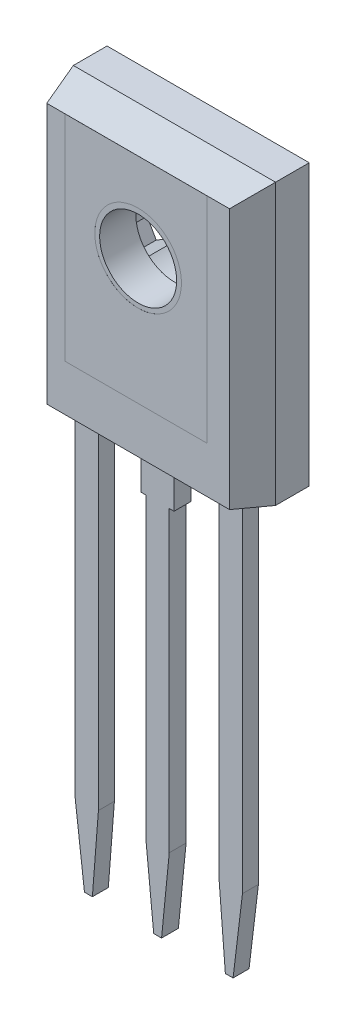
SolidWorks part; units mm, degrees
ref_plane "Front Plane" through (0, 0, 0) normal (0, 0, 1) x (1, 0, 0)
ref_plane "Top Plane" through (0, 0, 0) normal (0, 1, 0) x (1, 0, 0)
ref_plane "Right Plane" through (0, 0, 0) normal (1, 0, 0) x (0, 0, -1)
sketch "Sketch1" plane through (0, 0, 0) normal (0, 0, 1) x (1, 0, 0)
  line L1 (-3.9, 5.4) -> (3.9, 5.4)
  line L2 (-3.9, 5.4) -> (-3.9, -5.4)
  line L3 (-3.9, -5.4) -> (3.9, -5.4)
  line L4 (3.9, 5.4) -> (3.9, -5.4)
  line L5 (-3.9, 5.4) -> (3.9, -5.4) construction
  line L6 (-3.9, -5.4) -> (3.9, 5.4) construction
  circle A0 centre (0, 1.6) radius 1.6
  point P0 (0, 0)
extrude "Boss-Extrude2" add sketch "Sketch1" along normal blind 1.3
sketch "Sketch3" plane through (0, 0, 1.3) normal (0, 0, 1) x (1, 0, 0)
  line L1 (-3.9, -5.4) -> (3.9, -5.4)
  line L2 (-3.9, -5.4) -> (-3.9, 5.4)
  line L3 (-3.9, 5.4) -> (3.9, 5.4)
  line L4 (3.9, -5.4) -> (3.9, 5.4)
extrude "Boss-Extrude3" add sketch "Sketch3" along normal blind 1.4 separate body
sketch "Sketch2" plane through (0, 0, 1.3) normal (0, 0, 1) x (1, 0, 0)
  line L0 (0, 0) -> (0, 4.4749) construction
  line L1 (2.5017, 0.733) -> (1.5662, 1.2731)
  line L2 (0, 4.2) -> (0.5, 4.2)
  line L3 (0, 4.2) -> (-0.5, 4.2)
  line L4 (-0.5, 4.2) -> (-0.5, 3.1199)
  line L5 (0.5, 4.2) -> (0.5, 3.1199)
  line L6 (-0.5, 3.1199) -> (0.5, 3.1199)
  line L7 (2.2517, 0.3) -> (2.5017, 0.733)
  line L8 (2.2517, 0.3) -> (2.0017, -0.133)
  line L9 (2.0017, -0.133) -> (1.0662, 0.4071)
  line L10 (1.5662, 1.2731) -> (1.0662, 0.4071)
  line L11 (-2.0017, -0.133) -> (-1.0662, 0.4071)
  line L12 (-2.2517, 0.3) -> (-2.0017, -0.133)
  line L13 (-2.2517, 0.3) -> (-2.5017, 0.733)
  line L14 (-2.5017, 0.733) -> (-1.5662, 1.2731)
  line L15 (-1.0662, 0.4071) -> (-1.5662, 1.2731)
  circle A0 centre (0, 1.6) radius 1.6 construction
  dimension "D1" = 3
extrude "Cut-Extrude2" cut sketch "Sketch2" against normal blind 2.5
chamfer "Chamfer2" distance 1.4 angle 15 4 edges at (0, 5.4, 2.7) (3.9, 0, 2.7) (0, -5.4, 2.7) (-3.9, 0, 2.7) first distance on face at (0, 5.4, 2) first distance on face at (3.9, 0, 2) first distance on face at (0, -5.4, 2) first distance on face at (-3.9, 0, 2)
sketch "Sketch9" plane through (0, 0, 2.7) normal (0, 0, 1) x (1, 0, 0)
  line L0 (3.5249, 5.0249) -> (-3.5249, 5.0249) construction
  line L1 (-2.815, 5.0249) -> (2.657, 5.0249)
  line L2 (-2.815, 5.0249) -> (-2.815, -3.2408)
  line L3 (-2.815, -3.2408) -> (2.657, -3.2408)
  line L4 (2.657, 5.0249) -> (2.657, -3.2408)
extrude "Boss-Extrude7" add sketch "Sketch9" along normal blind 0.001 separate body
sketch "Sketch4" plane through (0, 0, 1.3) normal (0, 0, -1) x (-1, 0, 0)
  circle A0 centre (0, 1.6) radius 1.4862
extrude "Cut-Extrude3" cut sketch "Sketch4" against normal blind 4.4
sketch "Sketch5" plane through (0, -5.4, 0) normal (0, -1, 0) x (1, 0, 0)
  line L0 (3.9, 0) -> (-3.9, 1.3) construction
  line L1 (-3.9, 0) -> (3.9, 1.3) construction
  line L2 (3.9, 1.3) -> (3.9, 0) construction
  line L3 (3.9, 0) -> (-3.9, 1.3) construction
  line L4 (0.635, 1.3) -> (-0.635, 1.3)
  line L5 (0.635, 1.3) -> (0.635, 1.95)
  line L6 (0.635, 1.95) -> (-0.635, 1.95)
  line L7 (-0.635, 1.3) -> (-0.635, 1.95)
  line L8 (0.635, 1.3) -> (-0.635, 1.95) construction
  line L9 (0.635, 1.95) -> (-0.635, 1.3) construction
  line L10 (-3.9, 1.3) -> (-3.9, 0) construction
  line L11 (-3.9, 0) -> (0, 0) construction
  line L12 (-3.9, 0) -> (3.9, 0) construction
  line L13 (0, 0) -> (0, 1.3) construction
  line L14 (-3.9, 1.3) -> (3.9, 1.3) construction
  point P6 (0, 1.625)
extrude "Boss-Extrude4" add sketch "Sketch5" along normal blind 1.5 and the other way blind 1.5 separate body
sketch "Sketch7" plane through (0, -5.4, 0) normal (0, -1, 0) x (1, 0, 0)
  line L1 (-3.228, 1.2882) -> (-2.328, 1.2882)
  line L2 (-3.228, 1.2882) -> (-3.228, 1.9044)
  line L3 (-3.228, 1.9044) -> (-2.328, 1.9044)
  line L4 (-2.328, 1.2882) -> (-2.328, 1.9044)
  line L5 (-3.228, 1.2882) -> (-2.328, 1.9044) construction
  line L6 (-3.228, 1.9044) -> (-2.328, 1.2882) construction
  point P0 (-2.778, 1.5963)
extrude "Boss-Extrude5" add sketch "Sketch7" along normal blind 16 and the other way blind 1.5
mirror "Mirror1" about plane through (0, 0, 0) normal (1, 0, 0) of "Boss-Extrude5"
sketch "Sketch8" plane through (0, -6.9, 0) normal (0, -1, 0) x (1, 0, 0)
  point P6 (-0.0842, 1.5299)
sketch "Sketch10" plane through (0, 0, 2.701) normal (0, 0, 1) x (1, 0, 0)
  circle A0 centre (0, 1.6155) radius 1.6718
extrude "Cut-Extrude4" cut sketch "Sketch10" against normal blind 0.001
sketch "Sketch11" plane through (0, 0, 1.9044) normal (0, 0, 1) x (1, 0, 0)
sketch "Sketch12" plane through (0, -6.9, 0) normal (0, -1, 0) x (1, 0, 0)
  line L0 (-0.635, 1.95) -> (0.635, 1.3) construction
  line L1 (0.635, 1.3) -> (0.635, 1.95) construction
  line L2 (0.635, 1.95) -> (-0.635, 1.3) construction
  line L3 (-0.635, 1.95) -> (-0.635, 1.3) construction
  line L4 (-0.635, 1.3) -> (0.635, 1.3) construction
  line L6 (-0.45, 1.95) -> (0.45, 1.95)
  line L7 (-0.45, 1.95) -> (-0.45, 1.3)
  line L8 (-0.45, 1.3) -> (0.45, 1.3)
  line L9 (0.45, 1.95) -> (0.45, 1.3)
  line L10 (-0.45, 1.95) -> (0.45, 1.3) construction
  line L11 (-0.45, 1.3) -> (0.45, 1.95) construction
  point P4 (0, 1.625)
extrude "Boss-Extrude8" add sketch "Sketch12" along normal blind 14.5 contours L8 L9 L6 L7
sketch "Sketch13" plane through (0, 0, 1.9044) normal (0, 0, 1) x (1, 0, 0)
  line L0 (-2.778, -21.4) -> (-2.778, -21.5767) construction
  line L1 (-2.328, -21.4) -> (-3.228, -21.4) construction
  line L2 (-2.778, -21.5767) -> (-2.5613, -21.5767) construction
  line L3 (-2.5613, -21.5767) -> (-2.8658, -21.5767) construction
  line L4 (-2.8658, -21.5767) -> (-2.8658, -21.4) construction
  line L5 (-2.8658, -21.4) -> (-2.5613, -21.4) construction
  line L6 (-2.5613, -21.4) -> (-2.5613, -21.5767) construction
  line L7 (-2.778, -21.4) -> (-2.6836, -20.4013) construction
  line L8 (-2.6836, -20.4013) -> (-3.228, -20.4013) construction
  line L9 (-3.228, -5.238) -> (-3.228, -21.4) construction
  line L10 (-3.228, -20.4013) -> (-2.328, -20.4013) construction
  line L11 (-2.328, -5.238) -> (-2.328, -21.4) construction
  line L12 (-3.228, -20.4013) -> (-2.8658, -21.4) construction
  line L13 (-2.5613, -21.4) -> (-2.328, -20.4013) construction
  line L14 (-2.6836, -20.4013) -> (-2.6836, -18.4013) construction
  line L15 (-2.6836, -18.4013) -> (-2.328, -18.4013) construction
  line L16 (-2.328, -18.4013) -> (-2.5613, -21.4) construction
  line L17 (-2.6836, -18.4013) -> (-3.228, -18.4013) construction
  line L18 (-3.228, -18.4013) -> (-2.8658, -21.4) construction
  line L19 (-2.8658, -21.4) -> (-2.5613, -21.4) construction
  line L20 (-3.228, -18.4013) -> (-2.8658, -21.4)
  line L21 (-2.8658, -21.4) -> (-2.5613, -21.4)
  line L22 (-2.5613, -21.4) -> (-2.328, -18.4013)
  line L23 (-2.328, -18.4013) -> (-2.328, -21.4)
  line L24 (-2.328, -21.4) -> (-2.5613, -21.4)
  line L25 (-2.8658, -21.4) -> (-3.228, -21.4)
  line L26 (-3.228, -21.4) -> (-3.228, -18.4013)
extrude "Cut-Extrude6" cut sketch "Sketch13" against normal blind 15 contours L22 L5 L6 | L25 L26 L20 region at (-2.4058, -20.4004, 1.9044)
sketch "Sketch14" plane through (0, 0, 1.95) normal (0, 0, 1) x (1, 0, 0)
  line L0 (0, -21.4) -> (0, -21.7336) construction
  line L1 (-0.45, -21.4) -> (0.45, -21.4) construction
  line L2 (0, -21.7336) -> (0.1531, -21.7336) construction
  line L3 (0.1531, -21.7336) -> (-0.1502, -21.7336) construction
  line L4 (-0.1502, -21.7336) -> (-0.1502, -21.4) construction
  line L5 (-0.1502, -21.4) -> (0.1531, -21.4) construction
  line L6 (0.1531, -21.4) -> (0.1531, -21.7336) construction
  line L7 (0, -21.4) -> (0, -18.4) construction
  line L8 (0, -18.4) -> (0.45, -18.4) construction
  line L9 (0.45, -21.4) -> (0.45, -6.9) construction
  line L10 (0, -18.4) -> (-0.45, -18.4) construction
  line L11 (-0.45, -21.4) -> (-0.45, -6.9) construction
  line L12 (-0.45, -18.4) -> (-0.1502, -21.4)
  line L13 (-0.1502, -21.4) -> (0.1531, -21.4)
  line L14 (0.1531, -21.4) -> (0.45, -18.4)
  line L15 (-0.1502, -21.4) -> (-0.45, -21.4)
  line L16 (-0.45, -21.4) -> (-0.45, -18.4)
  line L17 (0.1531, -21.4) -> (0.45, -21.4)
  line L18 (0.45, -21.4) -> (0.45, -18.4)
  line M5 (-0.45, -21.4) -> (0.45, -21.4)
  line M6 (0.45, -21.4) -> (0.45, -6.9)
extrude "Cut-Extrude7" cut sketch "Sketch14" against normal blind 15 contours L14 M5 M6 | L15 L16 L12 region at (0.351, -20.4, 1.95)
sketch "Sketch15" plane through (0, 0, 1.9044) normal (0, 0, 1) x (1, 0, 0)
  line L0 (2.778, -21.4) -> (2.778, -21.8275) construction
  line L1 (2.328, -21.4) -> (3.228, -21.4) construction
  line L2 (2.778, -21.8275) -> (2.8657, -21.8275) construction
  line L3 (2.8657, -21.8275) -> (2.5692, -21.8275) construction
  line L4 (2.5692, -21.8275) -> (2.5692, -21.4) construction
  line L5 (2.5692, -21.4) -> (2.8657, -21.4) construction
  line L6 (2.8657, -21.8275) -> (2.8657, -21.4) construction
  line L7 (2.778, -21.4) -> (2.778, -18.4) construction
  line L8 (2.778, -18.4) -> (3.228, -18.4) construction
  line L9 (3.228, -5.238) -> (3.228, -21.4) construction
  line L10 (3.228, -18.4) -> (2.8657, -21.4) construction
  line L11 (2.8657, -21.4) -> (2.5692, -21.4) construction
  line L12 (2.5692, -21.4) -> (2.328, -18.4) construction
  line L13 (2.328, -5.238) -> (2.328, -21.4) construction
  line L14 (2.328, -18.4) -> (2.778, -18.4) construction
  line L15 (2.328, -18.4) -> (2.5692, -21.4)
  line L16 (2.5692, -21.4) -> (2.8657, -21.4)
  line L17 (2.8657, -21.4) -> (3.228, -18.4)
  line L18 (3.228, -18.4) -> (3.228, -21.4)
  line L19 (3.228, -21.4) -> (2.8657, -21.4)
  line L20 (2.5692, -21.4) -> (2.328, -21.4)
  line L21 (2.328, -21.4) -> (2.328, -18.4)
  line M2 (2.328, -5.238) -> (2.328, -21.4)
  line M3 (2.328, -21.4) -> (3.228, -21.4)
  line M4 (3.228, -21.4) -> (3.228, -5.238)
extrude "Cut-Extrude8" cut sketch "Sketch15" against normal blind 15 contours L15 M2 M3 | L17 M3 M4 region at (3.1072, -20.4, 1.9044) region at (2.4084, -20.4, 1.9044)
sketch "Sketch16" plane through (0, 0, 1.95) normal (0, 0, 1) x (1, 0, 0)
sketch "Sketch19" plane through (0, 0, 0) normal (0, 0, -1) x (-1, 0, 0)
  circle A0 centre (2.4152, 3.8341) radius 0.5
  circle A1 centre (-2.2342, -1.2133) radius 0.5
extrude "Cut-Extrude10" cut sketch "Sketch19" against normal blind 0.1
sketch "Sketch20" plane through (0, 0, 0) normal (0, 0, -1) x (-1, 0, 0)
  text T0 "BD" font "Century Gothic" height 0.6
extrude "Cut-Extrude12" cut sketch "Sketch20" against normal blind 0.1
sketch "Sketch21" plane through (0, 0, 0) normal (0, 0, -1) x (-1, 0, 0)
  text T0 "140 - 16" font "Century Gothic" height 0.6
extrude "Cut-Extrude13" cut sketch "Sketch21" against normal blind 0.1
